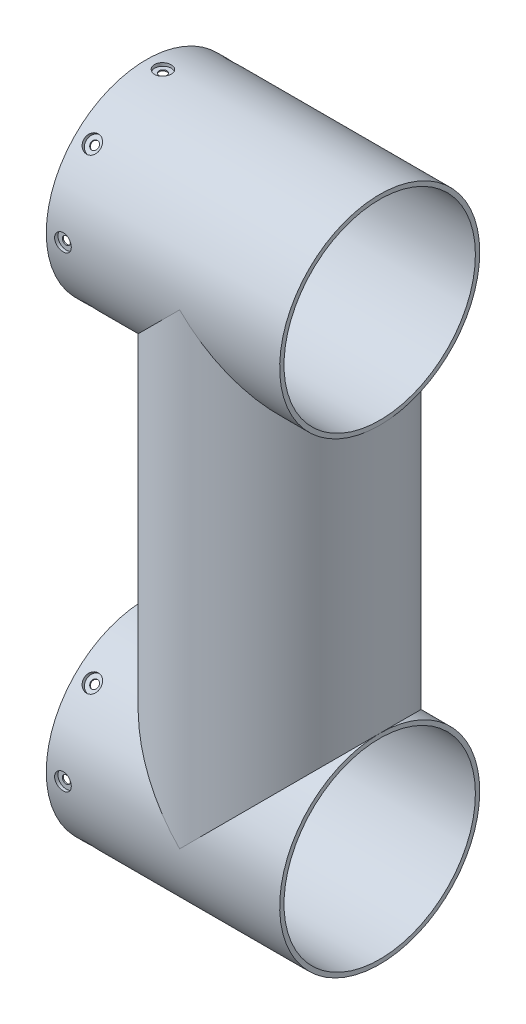
SolidWorks part; units mm, degrees
ref_plane "정면" through (0, 0, 0) normal (0, 0, 1) x (1, 0, 0)
ref_plane "윗면" through (0, 0, 0) normal (0, 1, 0) x (1, 0, 0)
ref_plane "우측면" through (0, 0, 0) normal (1, 0, 0) x (0, 0, -1)
sketch "스케치1" plane through (0, 0, 0) normal (0, 1, 0) x (1, 0, 0)
  circle A0 centre (0, 0) radius 30
  dimension "D1" = 60
extrude "보스-돌출1" add sketch "스케치1" along normal blind 140
sketch "스케치2" plane through (0, 0, 0) normal (1, 0, 0) x (0, 0, -1)
  circle A0 centre (0, 0) radius 30
extrude "보스-돌출2" add sketch "스케치2" along normal blind 30 and the other way blind 40
sketch "스케치3" plane through (30, 0, 0) normal (1, 0, 0) x (0, 0, -1)
  circle A0 centre (0, 0) radius 28.7
  circle A1 centre (0, 0) radius 30 construction
  dimension "D1" = 1.3
extrude "컷-돌출1" cut sketch "스케치3" against normal through all
sketch "스케치4" plane through (0, 140, 0) normal (0, 1, 0) x (1, 0, 0)
  circle A0 centre (0, 0) radius 28.7
  circle A1 centre (0, 0) radius 30 construction
  dimension "D1" = 1.3
extrude "컷-돌출2" cut sketch "스케치4" against normal blind 140
ref_plane "평면1" through (0, 0, 30) normal (0, 0, 1) x (1, 0, 0)
sketch "스케치5" plane through (0, 0, 30) normal (0, 0, 1) x (1, 0, 0)
  line L0 (-40, 30) -> (-40, -30) construction
  point P0 (-35, 0)
  point P1 (0, 0)
  dimension "D1" = 5
hole_wizard "M2 남비 머리 나사용 카운터보어1" positions "스케치6" profile "스케치7" counterbore size "M2" standard "ISO"
sketch "스케치6" plane through (0, 0, 30) normal (0, 0, 1) x (1, 0, 0)
  point P0 (-35, 0)
sketch "스케치7" plane through (-35, 0, 30) normal (1, 0, 0) x (0, -1, 0)
  line L0 (0, 0) -> (0, 10.721)
  line L1 (0, 10.721) -> (1.2, 10)
  line L2 (1.2, 10) -> (1.2, 1)
  line L3 (1.2, 1) -> (2.5, 1)
  line L4 (2.5, 1) -> (2.5, 0)
  line L5 (2.5, 0) -> (0, 0)
  line L10 (0, 10.721) -> (-1.2, 10) construction
  line L11 (0, -6.35) -> (0, 107.95) construction
  dimension "구멍 지름" = 2.4
  dimension "구멍 깊이" = 10
  dimension "카운터보어 지름" = 5
  dimension "카운터보어 깊이" = 1
  dimension "드릴 각도" = 118
pattern_circular "원형 패턴1" count 8 over 360 about axis through (-40, 0, 0) along (1, 0, 0) of "M2 남비 머리 나사용 카운터보어1"
ref_plane "평면2" through (0, 70, 0) normal (0, 1, 0) x (1, 0, 0)
mirror "대칭 복사2" about plane through (0, 70, 0) normal (0, 1, 0) of "컷-돌출1", "보스-돌출2", "M2 남비 머리 나사용 카운터보어1", "원형 패턴1"
